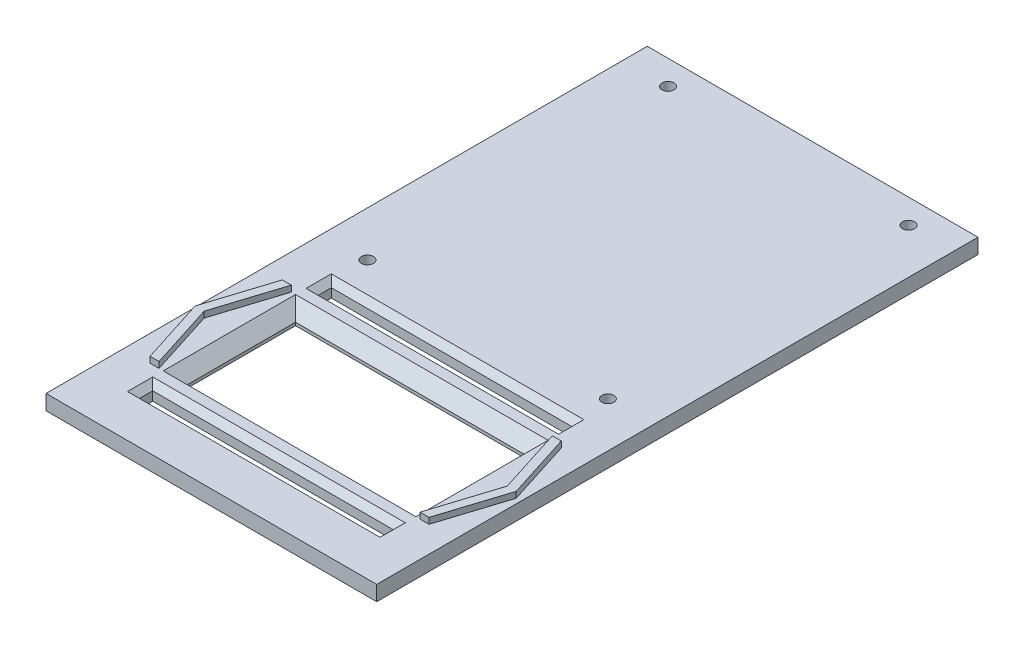
SolidWorks part; units mm, degrees
ref_plane "Front Plane" through (0, 0, 0) normal (0, 0, 1) x (1, 0, 0)
ref_plane "Top Plane" through (0, 0, 0) normal (0, 1, 0) x (1, 0, 0)
ref_plane "Right Plane" through (0, 0, 0) normal (1, 0, 0) x (0, 0, -1)
sketch "Sketch1" plane through (0, 0, 0) normal (0, 1, 0) x (1, 0, 0)
  line L1 (-69.85, -25.4) -> (69.85, -25.4)
  line L2 (-69.85, -25.4) -> (-69.85, 228.6)
  line L3 (-69.85, 228.6) -> (69.85, 228.6)
  line L4 (69.85, -25.4) -> (69.85, 228.6)
  line L5 (0, 228.6) -> (0, -25.4) construction
  line L6 (-69.85, 101.6) -> (69.85, 101.6) construction
  point P0 (0, 101.6)
  dimension "D1" = 254
  dimension "D2" = 139.7
  dimension "D3" = 101.6
extrude "Boss-Extrude1" add sketch "Sketch1" along normal blind 6.35
sketch "Sketch2" plane through (0, 6.35, 0) normal (0, 1, 0) x (1, 0, 0)
  line L0 (-69.85, -25.4) -> (69.85, -25.4) construction
  line L1 (-48.26, 12.7) -> (48.26, 12.7)
  line L2 (-48.26, 12.7) -> (-48.26, 58.42)
  line L3 (-48.26, 58.42) -> (48.26, 58.42)
  line L4 (48.26, 12.7) -> (48.26, 58.42)
  line L5 (0, 58.42) -> (0, 12.7) construction
  line L6 (-48.26, 35.56) -> (48.26, 35.56) construction
  point P0 (0, 35.56)
  dimension "D1" = 45.72
  dimension "D2" = 96.52
  dimension "D3" = 38.1
extrude "Main Hole" cut sketch "Sketch2" against normal through all
ref_plane "Plane1" through (0, 0, -35.56) normal (0, 0, 1) x (1, 0, 0)
sketch "Sketch3" plane through (0, 6.35, 0) normal (0, 1, 0) x (1, 0, 0)
  line L0 (48.26, 58.42) -> (-48.26, 58.42) construction
  line L1 (-50.8, 70.485) -> (50.8, 70.485)
  line L2 (-50.8, 70.485) -> (-50.8, 76.073)
  line L3 (-50.8, 76.073) -> (50.8, 76.073)
  line L4 (50.8, 70.485) -> (50.8, 76.073)
  point P4 (0, 70.485)
  dimension "D1" = 101.6
  dimension "D2" = 5.588
  dimension "D3" = 12.065
extrude "NeoPixel" cut sketch "Sketch3" against normal through all
mirror "Mirror2" about plane through (0, 0, -35.56) normal (0, 0, 1) of "NeoPixel"
sketch "Sketch5" plane through (0, 0, 0) normal (0, -1, 0) x (1, 0, 0)
  line L0 (69.85, -228.6) -> (-69.85, -228.6) construction
  line L1 (67.31, -226.06) -> (-67.31, -226.06)
  line L2 (67.31, -226.06) -> (67.31, 22.86)
  line L3 (67.31, 22.86) -> (-67.31, 22.86)
  line L4 (-67.31, -226.06) -> (-67.31, 22.86)
  line L5 (64.77, -223.52) -> (-64.77, -223.52)
  line L6 (64.77, -223.52) -> (64.77, 20.32)
  line L7 (64.77, 20.32) -> (-64.77, 20.32)
  line L8 (-64.77, -223.52) -> (-64.77, 20.32)
  line L9 (-69.85, -228.6) -> (-69.85, 25.4) construction
  line L10 (-69.85, 25.4) -> (69.85, 25.4) construction
  line L11 (69.85, 25.4) -> (69.85, -228.6) construction
  dimension "D1" = 2.54
  dimension "D2" = 2.54
  dimension "D3" = 2.54
  dimension "D4" = 2.54
  dimension "D5" = 2.54
  dimension "D6" = 2.54
  dimension "D7" = 2.54
  dimension "D8" = 2.54
extrude "Boss-Extrude2" [suppressed] add sketch "Sketch5" along normal blind 2.54 contours L4 L1 L2 L3 L5 L8 L7 L6
chamfer "Chamfer1" distance 2.54 angle 45 8 edges at (50.8, 6.35, 2.159) (0, 6.35, 4.953) (-50.8, 6.35, 2.159) (0, 6.35, -0.635) (-50.8, 6.35, -73.279) (0, 6.35, -70.485) (50.8, 6.35, -73.279) (0, 6.35, -76.073)
chamfer "Chamfer2" distance 5.08 angle 45 4 edges at (48.26, 6.35, -35.56) (0, 6.35, -12.7) (-48.26, 6.35, -35.56) (0, 6.35, -58.42)
sketch "Sketch6" plane through (0, 0, 0) normal (0, -1, 0) x (1, 0, 0)
  line L0 (0.6985, -35.56) -> (-0.6985, -35.56) construction
  line L1 (50.8, -10.16) -> (-50.8, -10.16)
  line L2 (50.8, -10.16) -> (50.8, -60.96)
  line L3 (50.8, -60.96) -> (-50.8, -60.96)
  line L4 (-50.8, -10.16) -> (-50.8, -60.96)
  line L5 (0, -60.96) -> (0, -10.16) construction
  line L6 (50.8, -35.56) -> (-50.8, -35.56) construction
  line L7 (0, -4.8895) -> (0, 4.8895) construction
  line L8 (6.35, -63.5) -> (6.35, -60.96)
  line L9 (53.34, -7.62) -> (-53.34, -7.62)
  line L10 (53.34, -7.62) -> (53.34, -63.5)
  line L11 (53.34, -63.5) -> (-53.34, -63.5)
  line L12 (-53.34, -7.62) -> (-53.34, -63.5)
  line L13 (0, -63.5) -> (0, -7.62) construction
  line L14 (53.34, -35.56) -> (-53.34, -35.56) construction
  line L31 (-6.35, -63.5) -> (-6.35, -60.96)
  line L32 (6.35, -62.23) -> (-6.35, -62.23) construction
  point P0 (0, -35.56)
  point P8 (0, -35.56)
  point P16 (0, -62.23)
  dimension "D1" = 2.54
  dimension "D2" = 2.54
  dimension "D3" = 50.8
  dimension "D4" = 101.6
  dimension "D5" = 12.7
extrude "Boss-Extrude3" [suppressed] add sketch "Sketch6" along normal blind 4.064 contours L9 L12 L11 L10 L4 L1 L2 L3
sketch "Sketch7" plane through (0, 6.35, 0) normal (0, 1, 0) x (1, 0, 0)
  line L0 (-50.8, 91.313) -> (50.8, 91.313) construction
  line L1 (0, -4.8895) -> (0, 4.8895) construction
  line L2 (-53.34, 78.613) -> (53.34, 78.613) construction
  circle A0 centre (50.8, 91.313) radius 2.54
  circle A1 centre (-50.8, 91.313) radius 2.54
  circle A2 centre (-50.8, 218.313) radius 2.54
  circle A3 centre (50.8, 218.313) radius 2.54
  point P4 (0, 91.313)
  point P9 (0, 0)
  point P10 (0, 0)
  dimension "D1" = 5.08
  dimension "D3" = 12.7
  dimension "D5" = 127
  dimension "D2" = 101.6
  dimension "D4" = 2
extrude "Cut-Extrude1" cut sketch "Sketch7" against normal up to next
sketch "Sketch8" plane through (0, 6.35, 0) normal (0, 1, 0) x (1, 0, 0)
  line L0 (58.928, 63.5) -> (67.818, 35.56)
  line L1 (67.818, 35.56) -> (58.928, 7.62)
  line L2 (58.928, 7.62) -> (55.118, 7.62)
  line L3 (55.118, 7.62) -> (64.008, 35.56)
  line L4 (64.008, 35.56) -> (55.118, 63.5)
  line L5 (55.118, 63.5) -> (58.928, 63.5)
  line L6 (64.008, 35.56) -> (67.818, 35.56) construction
  line L7 (-53.34, 63.5) -> (53.34, 63.5) construction
  line L8 (-0.6985, 35.56) -> (0.6985, 35.56) construction
  line L9 (53.34, 7.62) -> (-53.34, 7.62) construction
  point P12 (0, 0)
  dimension "D1" = 3.81
  dimension "D2" = 8.89
  dimension "D3" = 1.778
extrude "Boss-Extrude4" add sketch "Sketch8" along normal blind 2.54
mirror "Mirror3" about plane through (0, 0, 0) normal (1, 0, 0) of "Boss-Extrude4"
equation "\"D1@Sketch2\"=1.8in"
equation "\"D2@Sketch2\"=3.8in"
